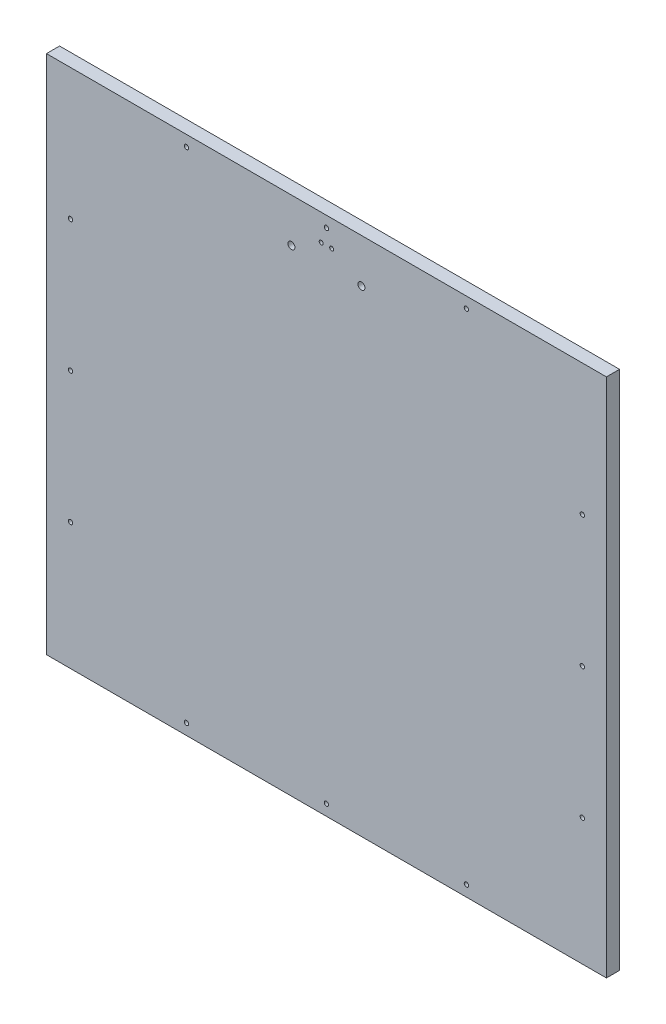
SolidWorks part; units mm, degrees
material "西洋杉"
ref_plane "正面" through (0, 0, 0) normal (0, 0, 1) x (1, 0, 0)
ref_plane "平面" through (0, 0, 0) normal (0, 1, 0) x (1, 0, 0)
ref_plane "右側面" through (0, 0, 0) normal (1, 0, 0) x (0, 0, -1)
sketch "ｽｹｯﾁ1" plane through (0, 0, 0) normal (0, 0, 1) x (1, 0, 0)
  line L1 (-320, 297.5) -> (320, 297.5)
  line L2 (-320, 297.5) -> (-320, -297.5)
  line L3 (-320, -297.5) -> (320, -297.5)
  line L4 (320, 297.5) -> (320, -297.5)
  line L5 (-320, 297.5) -> (320, -297.5) construction
  line L6 (-320, -297.5) -> (320, 297.5) construction
  point P0 (0, 0)
  dimension "D1" = 595
  dimension "D2" = 640
extrude "ﾎﾞｽ - 押し出し1" add sketch "ｽｹｯﾁ1" along normal blind 15
sketch "ｽｹｯﾁ2" plane through (0, 0, 15) normal (0, 0, 1) x (1, 0, 0)
  line L0 (-292.5, 297.5) -> (-292.5, -297.5) construction
  line L1 (320, 297.5) -> (-320, 297.5) construction
  line L2 (-320, -297.5) -> (320, -297.5) construction
  line L3 (-320, 297.5) -> (-320, -297.5) construction
  line L4 (-320, 285) -> (320, 285) construction
  line L5 (320, -297.5) -> (320, 297.5) construction
  circle A0 centre (-292.5, 147.5) radius 2.5
  circle A1 centre (-292.5, -2.5) radius 2.5
  circle A2 centre (-292.5, -152.5) radius 2.5
  circle A3 centre (-160, 285) radius 2.5
  circle A4 centre (0, 285) radius 2.5
  circle A5 centre (160, 285) radius 2.5
  dimension "D2" = 5
  dimension "D4" = 3
  dimension "D7" = 5
  dimension "D8" = 160
  dimension "D11" = 150
  dimension "D1" = 27.5
  dimension "D3" = 150
  dimension "D5" = 12.5
  dimension "D6" = 640
  dimension "D10" = 595
  dimension "D9" = 3
extrude "ｶｯﾄ - 押し出し1" cut sketch "ｽｹｯﾁ2" against normal through all contours A3 | A4 | A5
extrude "ｶｯﾄ - 押し出し2" cut sketch "ｽｹｯﾁ2<3>" against normal through all contours A0 | A1 | A2
sketch "ｽｹｯﾁ2<3>" plane through (0, 0, 15) normal (0, 0, 1) x (1, 0, 0) same geometry as "ｽｹｯﾁ2"
mirror "ﾐﾗｰ1" about plane through (0, 0, 0) normal (0, 1, 0) of "ｶｯﾄ - 押し出し1"
mirror "ﾐﾗｰ2" about plane through (0, 0, 0) normal (1, 0, 0) of "ｶｯﾄ - 押し出し2"
sketch "ｽｹｯﾁ3" plane through (0, 0, 0) normal (0, 0, -1) x (-1, 0, 0)
  line L0 (-320, 247.5) -> (320, 247.5) construction
  line L1 (-320, -297.5) -> (-320, 297.5) construction
  line L2 (320, 297.5) -> (320, -297.5) construction
  line L3 (-320, 297.5) -> (320, 297.5) construction
  circle A0 centre (-40, 247.5) radius 4
  circle A1 centre (40, 247.5) radius 4
  point P12 (0, 247.5)
  dimension "D4" = 8
  dimension "D5" = 8
  dimension "D1" = 50
  dimension "D2" = 80
  dimension "D3" = 40
extrude "ｶｯﾄ - 押し出し3" cut sketch "ｽｹｯﾁ3" against normal through all
sketch "ｽｹｯﾁ4" plane through (0, 0, 15) normal (0, 0, 1) x (1, 0, 0)
  line L0 (320, 297.5) -> (-320, 297.5) construction
  circle A0 centre (6, 267.5) radius 2.25
  dimension "D1" = 4.5
  dimension "D2" = 30
  dimension "D3" = 6
extrude "ｶｯﾄ - 押し出し4" cut sketch "ｽｹｯﾁ4" against normal through all
mirror "ﾐﾗｰ3" about plane through (0, 0, 0) normal (1, 0, 0) of "ｶｯﾄ - 押し出し4"
equation "\"D5@ｽｹｯﾁ3\"=\"D4@ｽｹｯﾁ3\""
